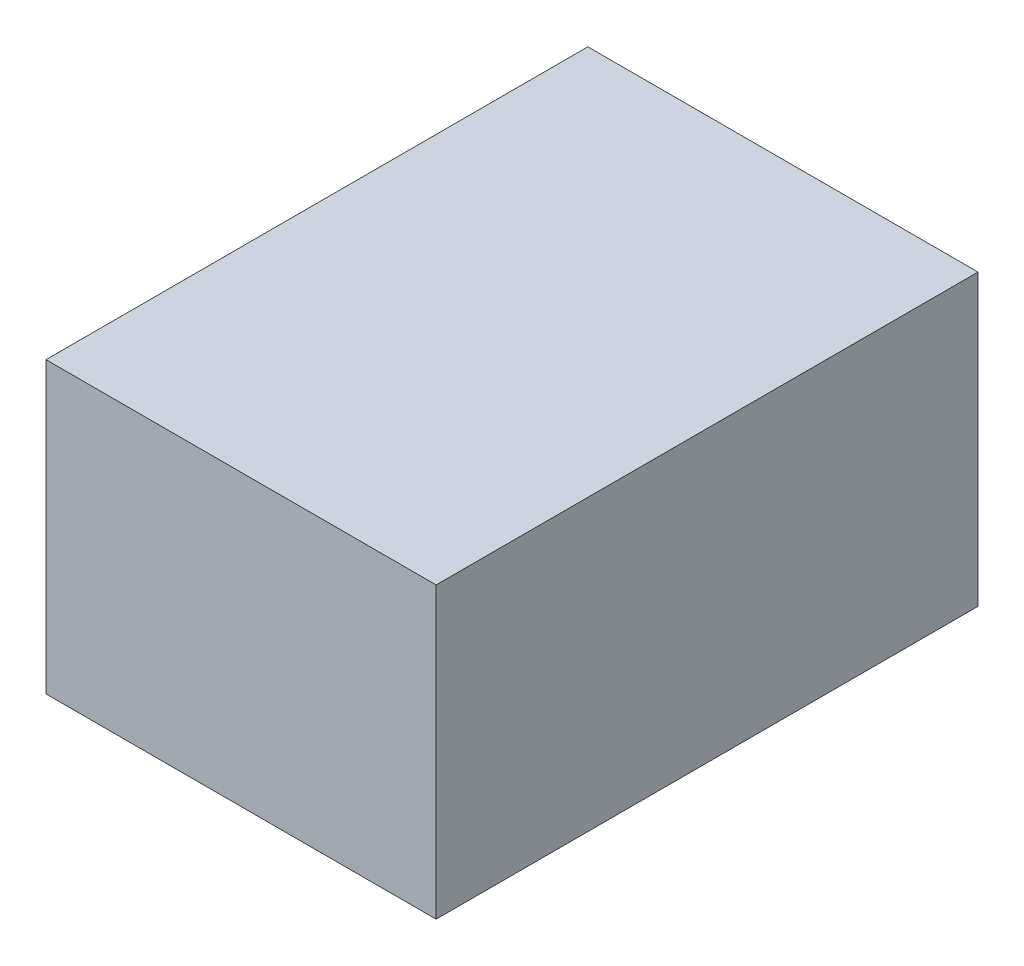
SolidWorks part; units mm, degrees
ref_plane "Front Plane" through (0, 0, 0) normal (0, 0, 1) x (1, 0, 0)
ref_plane "Top Plane" through (0, 0, 0) normal (0, 1, 0) x (1, 0, 0)
ref_plane "Right Plane" through (0, 0, 0) normal (1, 0, 0) x (0, 0, -1)
sketch "Sketch1" plane through (0, 0, 0) normal (0, 1, 0) x (1, 0, 0)
  line L1 (-32.004, -44.45) -> (32.004, -44.45)
  line L2 (-32.004, -44.45) -> (-32.004, 44.45)
  line L3 (-32.004, 44.45) -> (32.004, 44.45)
  line L4 (32.004, -44.45) -> (32.004, 44.45)
  line L5 (-32.004, -44.45) -> (32.004, 44.45) construction
  line L6 (-32.004, 44.45) -> (32.004, -44.45) construction
  point P0 (0, 0)
  dimension "D1" = 88.9
  dimension "D2" = 64.008
extrude "Boss-Extrude1" add sketch "Sketch1" along normal blind 23.749 and the other way blind 23.749
